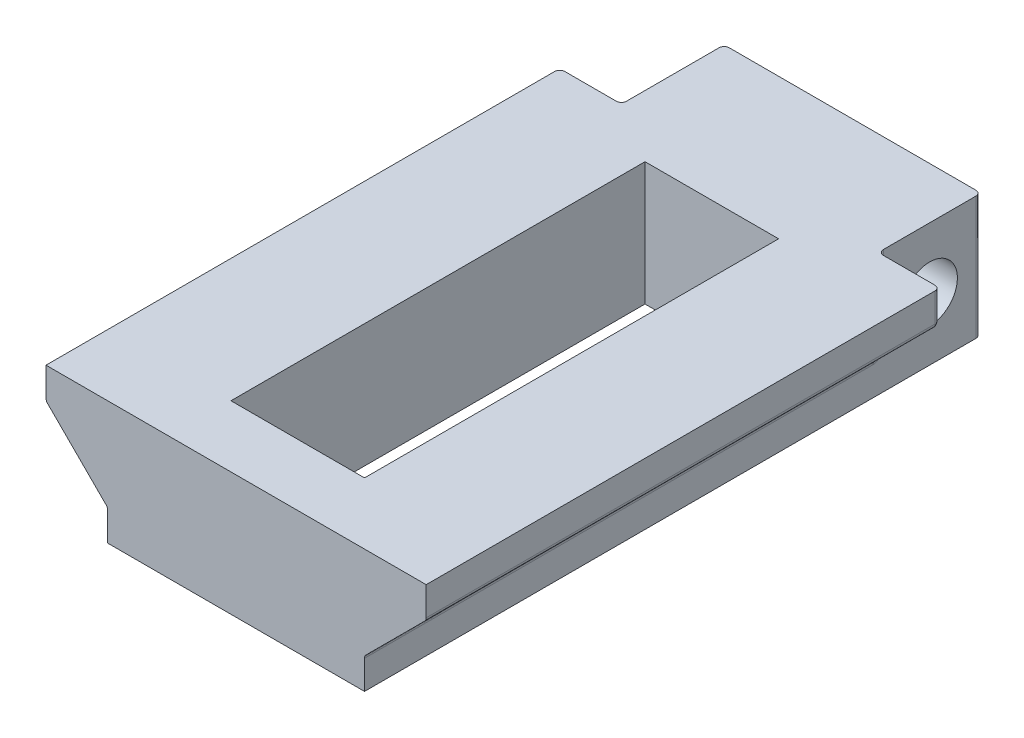
SolidWorks part; units mm, degrees
material "ABS"
ref_plane "Front Plane" through (0, 0, 0) normal (0, 0, 1) x (1, 0, 0)
ref_plane "Top Plane" through (0, 0, 0) normal (0, 1, 0) x (1, 0, 0)
ref_plane "Right Plane" through (0, 0, 0) normal (1, 0, 0) x (0, 0, -1)
sketch "Sketch1" plane through (0, 0, 0) normal (0, 0, 1) x (1, 0, 0)
  line L0 (0, 0) -> (0, 12) construction
  line L1 (-18.5, 12) -> (-18.5, 9)
  line L2 (-18.5, 9) -> (-12.5, 3)
  line L3 (-12.5, 3) -> (-12.5, 0)
  line L4 (12.5, 3) -> (12.5, 0)
  line L5 (18.5, 9) -> (12.5, 3)
  line L6 (18.5, 12) -> (18.5, 9)
  line L7 (-18.5, 12) -> (18.5, 12)
  line L8 (-12.5, 0) -> (12.5, 0)
  dimension "D1" = 12
  dimension "D2" = 3
  dimension "D3" = 45
  dimension "D4" = 25
extrude "Dovetail Body" add sketch "Sketch1" along normal mid plane 60
sketch "Sketch9" plane through (0, 0, -30) normal (0, 0, -1) x (-1, 0, 0)
  line L0 (0, 12) -> (0, 0) construction
  line L1 (-18.5, 12) -> (-12.5, 12)
  line L2 (-18.5, 12) -> (-18.5, 0)
  line L3 (-18.5, 0) -> (-12.5, 0)
  line L4 (-12.5, 12) -> (-12.5, 0)
  line L5 (-18.5, 12) -> (18.5, 12) construction
  line L6 (12.5, 0) -> (-12.5, 0) construction
  line L7 (12.5, 12) -> (12.5, 0)
  line L8 (18.5, 0) -> (12.5, 0)
  line L9 (18.5, 12) -> (18.5, 0)
  line L10 (18.5, 12) -> (12.5, 12)
extrude "Bolt Clearance" cut sketch "Sketch9" against normal blind 10
sketch "Sketch10" plane through (12.5, 0, 0) normal (1, 0, 0) x (0, 0, -1)
  line L0 (25, 12) -> (25, 0) construction
  line L1 (20, 12) -> (30, 12) construction
  line L2 (-30, 0) -> (30, 0) construction
  circle A0 centre (25, 6) radius 2.7
  dimension "D1" = 5.4
extrude "Bolt Insert" cut sketch "Sketch10" against normal through all
sketch "Sketch11" plane through (0, 0, 0) normal (0, -1, 0) x (1, 0, 0)
  line L0 (0, -16.3) -> (0, 0) construction
  line L1 (6.5, -16.3) -> (-6.5, -16.3)
  line L2 (6.5, -16.3) -> (6.5, 24)
  line L3 (6.5, 24) -> (-6.5, 24)
  line L4 (-6.5, -16.3) -> (-6.5, 24)
  line L5 (12.5, 30) -> (12.5, -30) construction
  line L6 (-12.5, 30) -> (12.5, 30) construction
  line L7 (12.5, -27.7) -> (12.5, -22.3) construction
  line L8 (12.5, -27.7) -> (12.5, -22.3) construction
  dimension "D1" = 6
  dimension "D2" = 6
  dimension "D3" = 6
extrude "Weight Clearance" cut sketch "Sketch11" against normal through all
fillet "Contouring" radius 0.5 12 edges at (12.5, 7.5, -20) (-12.5, 7.5, -20) (12.5, 3, 5) (-12.5, 3, 5) (-18.5, 9, 5) (18.5, 9, 5) (-15.5, 6, -20) (-18.5, 10.5, -20) (-12.5, 6, -30) (12.5, 6, -30) (15.5, 6, -20) (18.5, 10.5, -20)
equation "\"width keep\"= 3"
equation "\"dovetail height\"= 12"
equation "\"dovetail angle\"= 45"
equation "\"dovetail width\"= 25"
equation "\"D1@Sketch1\"=\"dovetail height\""
equation "\"D2@Sketch1\"=\"width keep\""
equation "\"D3@Sketch1\"=\"dovetail angle\""
equation "\"D4@Sketch1\"=\"dovetail width\""
equation "\"dovetail length\"= 60"
equation "\"D1@Dovetail Body\"=\"dovetail length\""
equation "\"print free\"= 0.35"
equation "\"print fit\"= 0.15"
equation "\"D1@Sketch11\"=2*\"width keep\""
equation "\"D2@Sketch11\"=\"D1@Sketch11\""
equation "\"D3@Sketch11\"=\"D2@Sketch11\""
